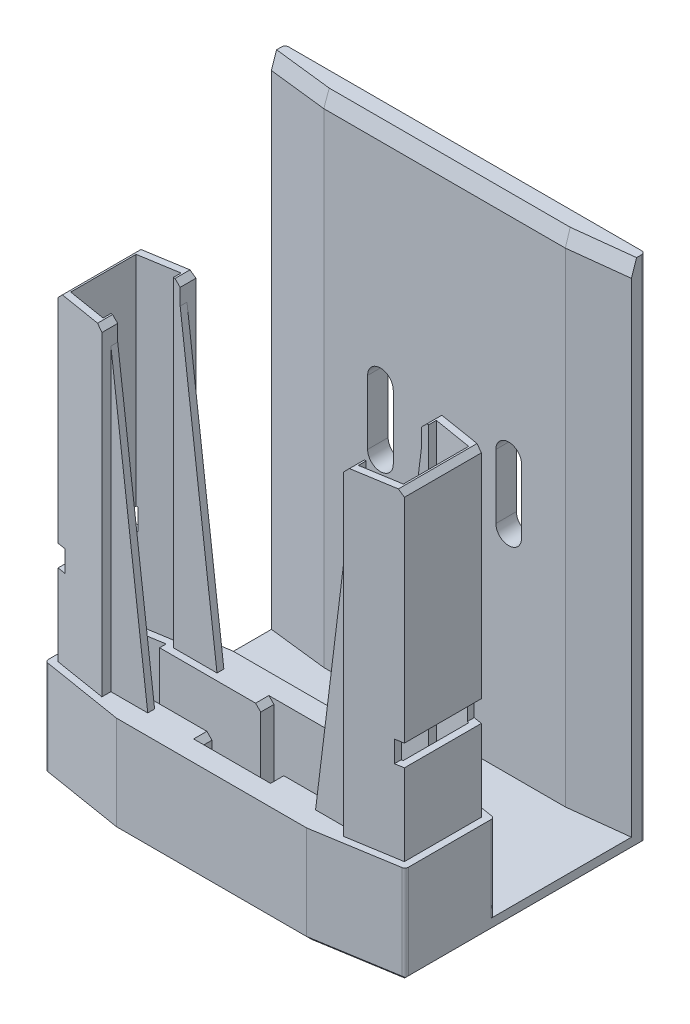
SolidWorks part; units mm, degrees
ref_plane "Front" through (0, 0, 0) normal (0, 0, 1) x (1, 0, 0)
ref_plane "Top" through (0, 0, 0) normal (0, 1, 0) x (1, 0, 0)
ref_plane "Right" through (0, 0, 0) normal (1, 0, 0) x (0, 0, -1)
sketch "Sketch1" plane through (0, 0, 0) normal (0, 1, 0) x (1, 0, 0)
  line L0 (0, -738.6263) -> (0, 36192.6906) construction
  line L1 (-738.6263, 0) -> (36192.6906, 0) construction
  line L2 (-40.5, -9) -> (-40.5, 9)
  line L3 (-40.5, 9) -> (-28.25, 11)
  line L4 (-28.25, 11) -> (-28.25, 8.9)
  line L5 (-28.25, 8.9) -> (-11, 8.9)
  line L6 (-11, 8.9) -> (-11, 12)
  line L7 (-11, 12) -> (11, 12)
  line L8 (-11, -12) -> (11, -12)
  line L9 (-11, -8.9) -> (-11, -12)
  line L10 (-28.25, -8.9) -> (-11, -8.9)
  line L11 (-28.25, -11) -> (-28.25, -8.9)
  line L12 (-40.5, -9) -> (-28.25, -11)
  line L13 (40.5, -9) -> (28.25, -11)
  line L14 (28.25, -11) -> (28.25, -8.9)
  line L15 (28.25, -8.9) -> (11, -8.9)
  line L16 (11, -8.9) -> (11, -12)
  line L17 (11, 8.9) -> (11, 12)
  line L18 (28.25, 8.9) -> (11, 8.9)
  line L19 (28.25, 11) -> (28.25, 8.9)
  line L20 (40.5, 9) -> (28.25, 11)
  line L21 (40.5, -9) -> (40.5, 9)
  line L42 (-22.2548, 13.6) -> (22.2548, 13.6)
  line L43 (-42.1, -10.36) -> (-42.1, 10.36)
  line L44 (-42.1, 10.36) -> (-22.2548, 13.6)
  line L45 (42.1, 10.36) -> (22.2548, 13.6)
  line L46 (42.1, -10.36) -> (42.1, 10.36)
  line L47 (42.1, -10.36) -> (22.2548, -13.6)
  line L48 (-22.2548, -13.6) -> (22.2548, -13.6)
  line L49 (-42.1, -10.36) -> (-22.2548, -13.6)
  line L50 (-1066.7659, 42.5) -> (48933.2341, 42.5) construction
  line L51 (-1082.2929, -42.5) -> (48917.7071, -42.5) construction
  line L52 (-38.9, 7.64) -> (-29.85, 9.1176)
  line L53 (-29.85, 9.1176) -> (-29.85, 7.3)
  line L54 (-29.85, 7.3) -> (-9.4, 7.3)
  line L55 (-9.4, 7.3) -> (-9.4, 10.4)
  line L56 (-9.4, 10.4) -> (9.4, 10.4)
  line L57 (9.4, 7.3) -> (9.4, 10.4)
  line L58 (29.85, 7.3) -> (9.4, 7.3)
  line L59 (29.85, 9.1176) -> (29.85, 7.3)
  line L60 (38.9, 7.64) -> (29.85, 9.1176)
  line L61 (38.9, -7.64) -> (38.9, 7.64)
  line L62 (38.9, -7.64) -> (29.85, -9.1176)
  line L63 (29.85, -9.1176) -> (29.85, -7.3)
  line L64 (29.85, -7.3) -> (9.4, -7.3)
  line L65 (9.4, -7.3) -> (9.4, -10.4)
  line L66 (-9.4, -10.4) -> (9.4, -10.4)
  line L67 (-9.4, -7.3) -> (-9.4, -10.4)
  line L68 (-29.85, -7.3) -> (-9.4, -7.3)
  line L69 (-29.85, -9.1176) -> (-29.85, -7.3)
  line L70 (-38.9, -7.64) -> (-29.85, -9.1176)
  line L71 (-38.9, -7.64) -> (-38.9, 7.64)
  line L72 (-31.45, -5.7) -> (-7.8, -5.7)
  line L73 (-7.8, -5.7) -> (-7.8, -8.8)
  line L74 (-7.8, -8.8) -> (7.8, -8.8)
  line L75 (7.8, -5.7) -> (7.8, -8.8)
  line L76 (31.45, -5.7) -> (7.8, -5.7)
  line L77 (31.45, -7.2352) -> (31.45, -5.7)
  line L78 (37.3, -6.2801) -> (31.45, -7.2352)
  line L79 (37.3, -6.2801) -> (37.3, 6.2801)
  line L80 (37.3, 6.2801) -> (31.45, 7.2352)
  line L81 (31.45, 7.2352) -> (31.45, 5.7)
  line L82 (31.45, 5.7) -> (7.8, 5.7)
  line L83 (7.8, 5.7) -> (7.8, 8.8)
  line L84 (-7.8, 8.8) -> (7.8, 8.8)
  line L85 (-7.8, 5.7) -> (-7.8, 8.8)
  line L86 (-31.45, 5.7) -> (-7.8, 5.7)
  line L87 (-31.45, 7.2352) -> (-31.45, 5.7)
  line L88 (-37.3, 6.2801) -> (-31.45, 7.2352)
  line L89 (-37.3, -6.2801) -> (-37.3, 6.2801)
  line L90 (-37.3, -6.2801) -> (-31.45, -7.2352)
  line L91 (-31.45, -7.2352) -> (-31.45, -5.7)
  point P17 (-40.5, 0)
  point P22 (0, -12)
  point P23 (0, 12)
  point P27 (40.5, 0)
  point P54 (0, 13.6)
  point P57 (42.1, 0)
  point P60 (-42.1, 0)
  dimension "D1" = 81
  dimension "D2" = 24
  dimension "D4" = 18
  dimension "D5" = 17.25
  dimension "D6" = 12.25
  dimension "D7" = 3.1
  dimension "D9" = 85
  dimension "D10" = 42.5
  dimension "D11" = 1.6
  dimension "D12" = 1.6
  dimension "D13" = 1.6
  dimension "D3" = 22
  dimension "D8" = 1.6
  dimension "D15" = 1.6
extrude "Boss-Extrude1" add sketch "Sketch1" along normal blind 23.2 contours L49 L48 L47 L46 L45 L42 L44 L43
extrude "Boss-Extrude2" add sketch "Sketch1<3>" along normal blind 75 from surface contours L13 L21 L20 L19 L18 L17 L7 L6 L5 L4 L3 L2 L12 L11 L10 L9 L8 L16 L15 L14 L70 L71 L52 L53 L54 L55 L56 L57 L58 L59 L60 L61 L62 L63 L64 L65 L66 L67 L68 L69 region at (-39.6552, 0, 0) starting at face at (0, 23.2, 0)
sketch "Sketch1<3>" plane through (0, 0, 0) normal (0, 1, 0) x (1, 0, 0) same geometry as "Sketch1"
sketch "Sketch2" plane through (0, 0, 0) normal (0, 0, 1) x (1, 0, 0)
  line L0 (0, -1007.7521) -> (0, 48992.2479) construction
  line L2 (-40.5, 47.2) -> (-38.5, 47.2)
  line L3 (-40.5, 47.2) -> (-40.5, 42.2)
  line L4 (-40.5, 42.2) -> (-38.5, 42.2)
  line L5 (-38.5, 47.2) -> (-38.5, 42.2)
  line L6 (-40.5, 47.2) -> (-38.5, 42.2) construction
  line L7 (-40.5, 42.2) -> (-38.5, 47.2) construction
  line L8 (-40.5, 98.2) -> (-40.5, 23.2) construction
  line L9 (40.5, 42.2) -> (38.5, 47.2) construction
  line L10 (40.5, 47.2) -> (38.5, 42.2) construction
  line L11 (38.5, 47.2) -> (38.5, 42.2)
  line L12 (40.5, 42.2) -> (38.5, 42.2)
  line L13 (40.5, 47.2) -> (40.5, 42.2)
  line L14 (40.5, 47.2) -> (38.5, 47.2)
  line L15 (-40.5, 98.2) -> (-28.25, 98.2) construction
  point P1 (-39.5, 44.7)
  point P16 (39.5, 44.7)
  dimension "D1" = 2
  dimension "D2" = 5
  dimension "D3" = 51
extrude "Cut-Extrude1" cut sketch "Sketch2" against normal through all both and the other way through all
sketch "Sketch3" plane through (0, 0, 0) normal (0, 0, 1) x (1, 0, 0)
  line L0 (0, -1021.8671) -> (0, 48978.1329) construction
  line L2 (-11, 98.2) -> (11, 98.2) construction
  line L3 (-28.25, 93.2) -> (-19.625, 23.2)
  line L4 (-19.625, 23.2) -> (19.625, 23.2)
  line L5 (28.25, 93.2) -> (19.625, 23.2)
  line L6 (-19.625, -996.8) -> (-19.625, 49003.2) construction
  line L7 (-28.25, 23.2) -> (-11, 23.2) construction
  line L8 (19.625, -996.8) -> (19.625, 49003.2) construction
  line L9 (28.25, 23.2) -> (11, 23.2) construction
  line L10 (-28.25, 93.2) -> (-28.25, 98.2)
  line L11 (-28.25, 98.2) -> (28.25, 98.2)
  line L12 (28.25, 98.2) -> (28.25, 93.2)
  line L13 (-28.25, 98.2) -> (-28.25, 23.2) construction
  point P12 (0, 23.2)
  point P13 (0, 98.2)
  point P18 (-19.625, 23.2)
  point P23 (19.625, 23.2)
  dimension "D1" = 5
extrude "Cut-Extrude2" cut sketch "Sketch3" against normal through all both and the other way through all
extrude "Cut-Extrude3" cut sketch "Sketch1<4>" against normal through all and the other way through all contours L90 L91 L72 L73 L74 L75 L76 L77 L78 L79 L80 L81 L82 L83 L84 L85 L86 L87 L88 L89
sketch "Sketch1<4>" plane through (0, 0, 0) normal (0, 1, 0) x (1, 0, 0) same geometry as "Sketch1"
sketch "Sketch4" plane through (0, 0, 0) normal (0, 1, 0) x (1, 0, 0)
  line L0 (42.1, 10.36) -> (22.2548, 13.6) construction
  line L1 (-22.2548, 13.6) -> (22.2548, 13.6) construction
  line L2 (-42.1, 10.36) -> (-22.2548, 13.6) construction
  line L3 (42.1, 10.36) -> (22.2548, 13.6)
  line L4 (-22.2548, 13.6) -> (22.2548, 13.6)
  line L5 (-42.1, 10.36) -> (-22.2548, 13.6)
  line L6 (-42.1, 10.36) -> (-42.1, 42.5)
  line L7 (-42.1, 42.5) -> (42.1, 42.5)
  line L8 (42.1, 42.5) -> (42.1, 10.36)
  dimension "D1" = 42.5
extrude "Boss-Extrude3" add sketch "Sketch4" along normal blind 3.2
sketch "Sketch5" plane through (0, 0, 0) normal (0, 1, 0) x (1, 0, 0)
  line L1 (-42.1, 42.5) -> (42.1, 42.5)
  line L2 (-42.1, 42.5) -> (-42.1, 45.7)
  line L3 (-42.1, 45.7) -> (42.1, 45.7)
  line L4 (42.1, 42.5) -> (42.1, 45.7)
  line L6 (0, -1000) -> (0, 49000) construction
  line L7 (42.1, 42.5) -> (-42.1, 42.5) construction
  line L8 (-42.1, 42.5) -> (-42.1, 10.36) construction
  line L9 (42.1, 10.36) -> (42.1, 42.5) construction
  dimension "D1" = 3.2
extrude "Boss-Extrude4" add sketch "Sketch5" along normal blind 120
sketch "Sketch6" plane through (0, 0, 0) normal (0, 1, 0) x (1, 0, 0)
  line L0 (-42.1, 42.5) -> (42.1, 42.5) construction
  line L1 (-42.1, 42.5) -> (42.1, 42.5)
  line L2 (-28.25, 40.9) -> (28.25, 40.9)
  line L3 (-42.1, 42.5) -> (-28.25, 40.9)
  line L4 (0, -1000) -> (0, 49000) construction
  line L5 (-42.1, 40.9) -> (42.1, 40.9) construction
  line L6 (42.1, 42.5) -> (28.25, 40.9)
  line L7 (-28.25, 11) -> (-28.25, 7.3) construction
  dimension "D1" = 1.6
extrude "Boss-Extrude5" add sketch "Sketch6" along normal up to surface (120 mm away) up to face at (0, 120, -44.1)
sketch "Sketch7" plane through (0, 0, 0) normal (0, 0, -1) x (-1, 0, 0)
  line L5 (0, -971.4681) -> (0, 49028.5319) construction
  line L8 (-15, 67.5) -> (-15, 52.5) construction
  line L9 (-12, 67.5) -> (-12, 52.5)
  line L10 (-18, 67.5) -> (-18, 52.5)
  line L11 (15, 67.5) -> (15, 52.5) construction
  line L13 (12, 67.5) -> (12, 52.5)
  line L14 (18, 67.5) -> (18, 52.5)
  arc A0 (-12, 67.5) -> (-18, 67.5) centre (-15, 67.5) ccw
  arc A1 (-18, 52.5) -> (-12, 52.5) centre (-15, 52.5) ccw
  arc A2 (12, 67.5) -> (18, 67.5) centre (15, 67.5) cw
  arc A3 (18, 52.5) -> (12, 52.5) centre (15, 52.5) cw
  point P4 (-15, 60)
  point P11 (-25, 60)
  point P15 (15, 60)
  dimension "D1" = 3
  dimension "D2" = 15
  dimension "D3" = 15
  dimension "D4" = 60
extrude "Cut-Extrude4" cut sketch "Sketch7" against normal through all both and the other way through all
chamfer "Chamfer1" distance 3.6 distance2 1.2 3 edges at (-35.175, 120, -41.7) (35.175, 120, -41.7) (0, 120, -40.9) first distance on face at (-35.175, 61.6, -41.7) first distance on face at (35.175, 61.6, -41.7) first distance on face at (15, 60, -40.9)
chamfer "Chamfer2" distance 1.2 angle 45 18 edges at (42.1, 0, -17.67) (0, 0, -45.7) (-42.1, 0, -17.67) (0, 0, 13.6) (-32.1774, 0, 11.98) (32.1774, 0, 11.98) (40.5, 98.2, 0) (-40.5, 98.2, 0) (-7.8, 0, -7.25) (-7.8, 0, 7.25) (7.8, 23.2, 7.25) (7.8, 23.2, -7.25) (-7.8, 23.2, 7.25) (-7.8, 23.2, -7.25) (28.25, 98.2, -9.15) (28.25, 98.2, 9.15) (-28.25, 98.2, -9.15) (-28.25, 98.2, 9.15)
fillet "Fillet1" radius 0.8 6 edges at (42.1, 60.6, -45.7) (-42.1, 60.6, -45.7) (-42.1, 12.2, 10.36) (42.1, 12.2, 10.36) (-42.1, 13.2, -10.36) (42.1, 13.2, -10.36)
equation "\"D11@Sketch1\"=\"D8@Sketch1\""
equation "\"D12@Sketch1\"=\"D8@Sketch1\""
equation "\"D13@Sketch1\"=\"D8@Sketch1\""
